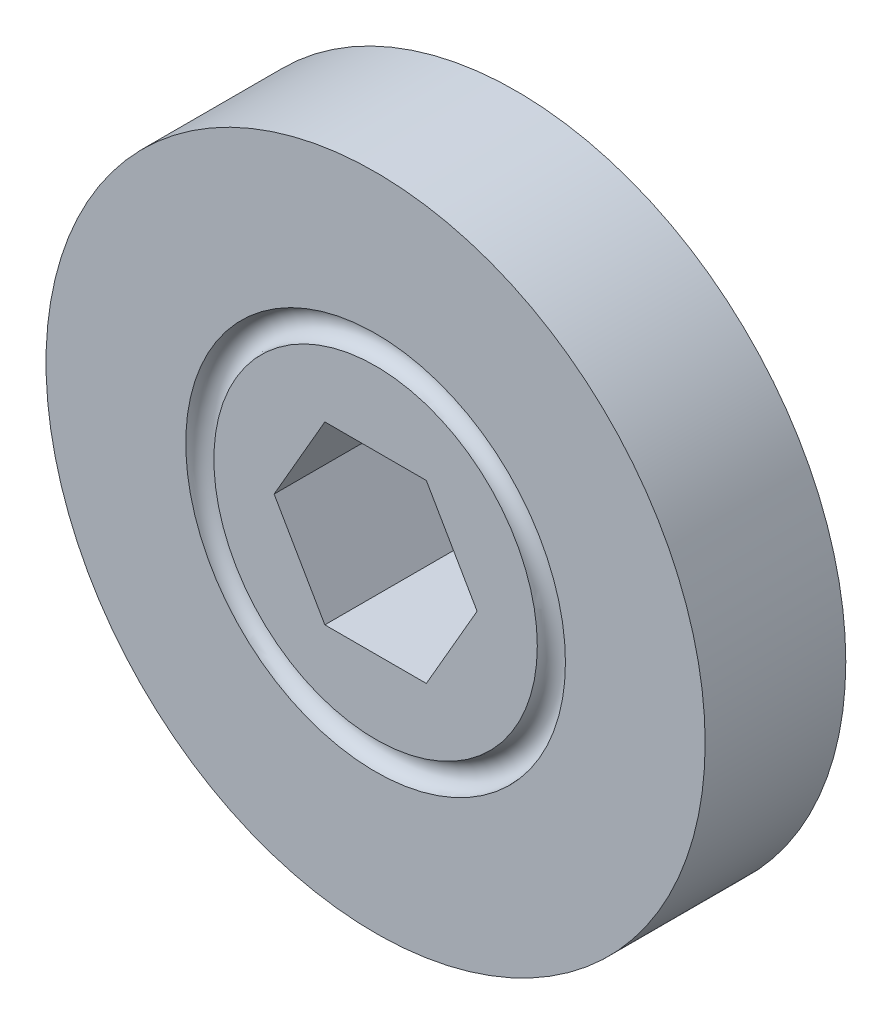
SolidWorks part; units mm, degrees
ref_plane "Front Plane" through (0, 0, 0) normal (0, 0, 1) x (1, 0, 0)
ref_plane "Top Plane" through (0, 0, 0) normal (0, 1, 0) x (1, 0, 0)
ref_plane "Right Plane" through (0, 0, 0) normal (1, 0, 0) x (0, 0, -1)
sketch "Sketch1" plane through (0, 0, 0) normal (1, 0, 0) x (0, 0, -1)
  line L0 (0, 0) -> (0, 23.8125) construction
  line L1 (-5.08, 23.8125) -> (5.08, 23.8125)
  line L2 (5.08, 23.8125) -> (5.08, 13.716)
  line L3 (5.08, 11.684) -> (5.08, 0)
  line L4 (-5.08, 11.684) -> (-5.08, 0)
  line L5 (-5.08, 23.8125) -> (-5.08, 13.716)
  line L6 (-5.08, 0) -> (5.08, 0)
  arc A0 (5.08, 13.716) -> (5.08, 11.684) centre (5.08, 12.7) ccw
  arc A1 (-5.08, 13.716) -> (-5.08, 11.684) centre (-5.08, 12.7) cw
  point P6 (0, 23.8125)
  dimension "D1" = 10.16
  dimension "D4" = 1.016
  dimension "D2" = 23.8125
  dimension "D3" = 12.7
revolve "Revolve1" add sketch "Sketch1" angle 360 about L6
sketch "Sketch2" plane through (0, 0, 5.08) normal (0, 0, 1) x (1, 0, 0)
  line L1 (-3.6662, 6.35) -> (-7.3323, 0)
  line L2 (-7.3323, 0) -> (-3.6662, -6.35)
  line L3 (-3.6662, -6.35) -> (3.6662, -6.35)
  line L4 (3.6662, -6.35) -> (7.3323, 0)
  line L5 (7.3323, 0) -> (3.6662, 6.35)
  line L6 (3.6662, 6.35) -> (-3.6662, 6.35)
  circle A0 centre (0, 0) radius 6.35 construction
  dimension "D1" = 12.7
extrude "Cut-Extrude1" cut sketch "Sketch2" against normal up to next
